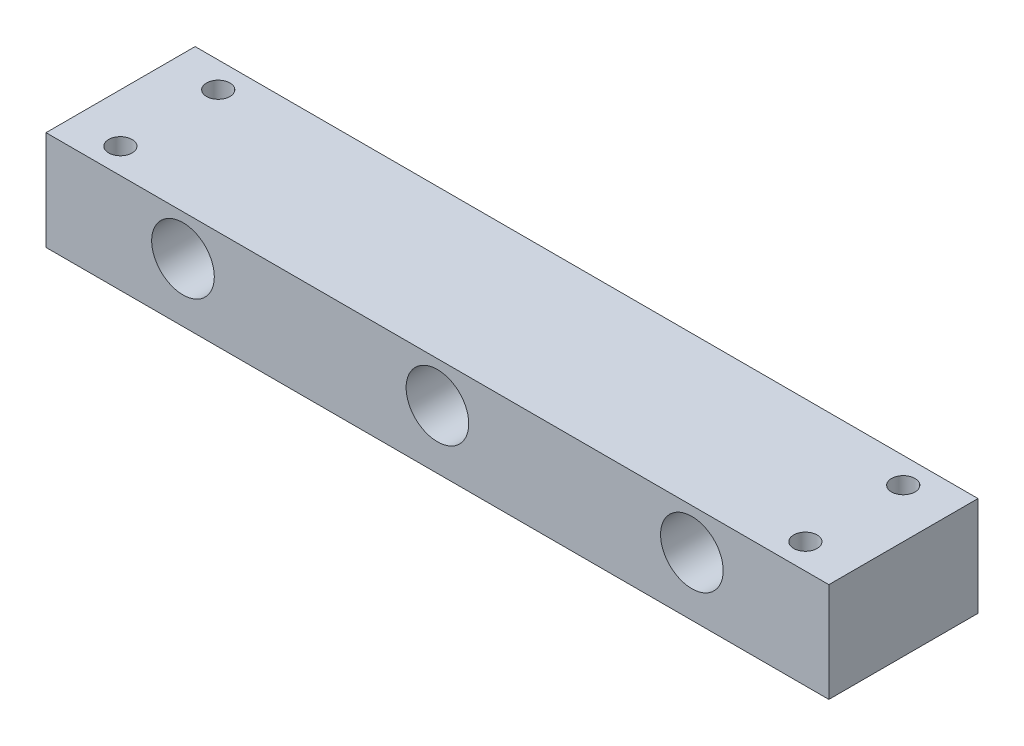
SolidWorks part; units mm, degrees
ref_plane "Front Plane" through (0, 0, 0) normal (0, 0, 1) x (1, 0, 0)
ref_plane "Top Plane" through (0, 0, 0) normal (0, 1, 0) x (1, 0, 0)
ref_plane "Right Plane" through (0, 0, 0) normal (1, 0, 0) x (0, 0, -1)
sketch "Sketch1" plane through (0, 0, 0) normal (0, 1, 0) x (1, 0, 0)
  line L1 (0, 0) -> (400, 0)
  line L2 (0, 0) -> (0, 76.2)
  line L3 (0, 76.2) -> (400, 76.2)
  line L4 (400, 0) -> (400, 76.2)
  dimension "D1" = 76.2
  dimension "D2" = 400
extrude "Boss-Extrude1" add sketch "Sketch1" along normal blind 50.8
sketch "Sketch3" plane through (0, 50.8, 0) normal (0, 1, 0) x (1, 0, 0)
  line L1 (0, 0) -> (200, 0)
  line L2 (0, 0) -> (0, 38)
  line L3 (0, 38) -> (200, 38)
  line L4 (200, 0) -> (200, 38)
  line L5 (25, 63) -> (375, 63)
  line L6 (25, 63) -> (25, 13)
  line L7 (25, 13) -> (375, 13)
  line L8 (375, 63) -> (375, 13)
  line L9 (25, 63) -> (375, 13) construction
  line L10 (25, 13) -> (375, 63) construction
  circle A0 centre (25, 63) radius 6
  circle A1 centre (25, 13) radius 6
  circle A2 centre (375, 63) radius 6
  circle A3 centre (375, 13) radius 6
  dimension "D1" = 200
  dimension "D2" = 38
  dimension "D3" = 350
  dimension "D4" = 50
extrude "Cut-Extrude2" cut sketch "Sketch3" against normal blind 50.8 contours A2 | A1 | A3 | A0
sketch "Sketch5" plane through (0, 0, 0) normal (0, 0, 1) x (1, 0, 0)
  line L0 (200, 30) -> (330, 30)
  line L1 (0, 0) -> (200, 0)
  line L2 (0, 0) -> (0, 30)
  line L4 (200, 0) -> (200, 30)
  line L5 (200, 30) -> (70, 30)
  circle A0 centre (200, 30) radius 16
  circle A1 centre (70, 30) radius 16
  circle A2 centre (330, 30) radius 16
  dimension "D3" = 130
  dimension "D1" = 30
  dimension "D2" = 200
  dimension "D4" = 130
extrude "Cut-Extrude3" cut sketch "Sketch5" against normal through all contours A1 | L0 A0 L5 | L4 A0 L0 | L5 A0 L4 | A2 region at (200, 36.7906, 0) region at (206.7906, 23.2094, 0) region at (193.2094, 23.2094, 0) region at (330, 45.5475, 0) region at (54.4525, 30, 0)
